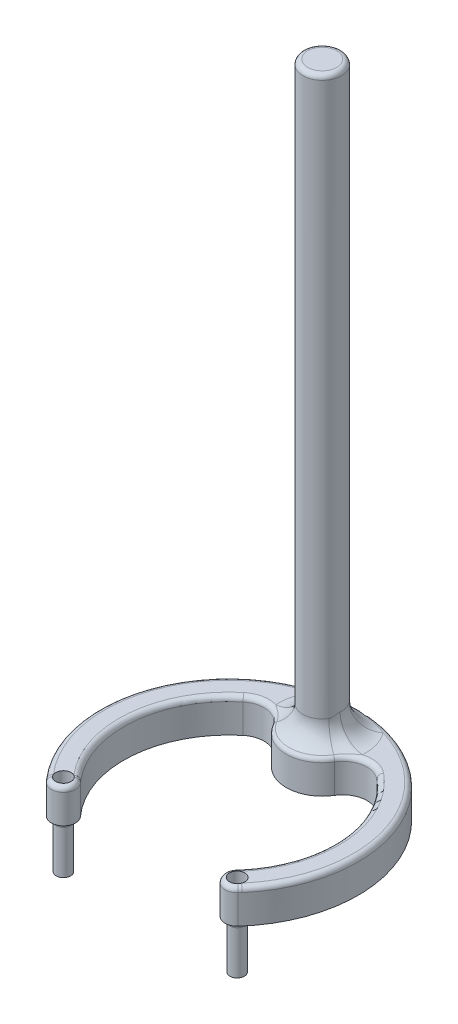
SolidWorks part; units mm, degrees
ref_plane "Front Plane" through (0, 0, 0) normal (0, 0, 1) x (1, 0, 0)
ref_plane "Top Plane" through (0, 0, 0) normal (0, 1, 0) x (1, 0, 0)
ref_plane "Right Plane" through (0, 0, 0) normal (1, 0, 0) x (0, 0, -1)
sketch "Sketch15" plane through (0, 0, 0) normal (0, 0, 1) x (1, 0, 0)
  point P0 (18, 0)
  point P1 (-18, 0)
  dimension "D1" = 18
  dimension "D2" = 18
sketch "Sketch17" plane through (0, 0, 0) normal (0, 1, 0) x (1, 0, 0)
  arc A0 (-19.8541, -1.6771) -> (-16.1459, 1.6771) centre (-18, 0) ccw
  arc A1 (16.1459, 1.6771) -> (19.8541, -1.6771) centre (18, 0) ccw
  arc A2 (19.8541, -1.6771) -> (-19.8541, -1.6771) centre (0, 16.2816) ccw
  arc A3 (16.1459, 1.6771) -> (13.851, 33.0785) centre (0, 16.2816) ccw
  arc A4 (16.1459, 1.6771) -> (19.8541, -1.6771) centre (18, 0) ccw
  arc A5 (-19.8541, -1.6771) -> (-16.1459, 1.6771) centre (-18, 0) ccw
  arc A6 (-6.3809, 31.7908) -> (6.3809, 31.7908) centre (0, 35.6141) ccw
  arc A7 (-13.851, 33.0785) -> (-16.1459, 1.6771) centre (0, 16.2816) ccw
  arc A8 (-6.3809, 31.7908) -> (-13.851, 33.0785) centre (-10.6699, 29.2209) ccw
  arc A9 (6.3809, 31.7908) -> (13.851, 33.0785) centre (10.6699, 29.2209) cw
  point P14 (-7.3474, 36.7755)
  dimension "D1" = 5
  dimension "D2" = 5
extrude "Boss-Extrude1" add sketch "Sketch17" along normal blind 7 contours A6 A9 A3 A1 A2 A0 A7 A8 region at (0, 0, -42.3498)
sketch "Sketch18" plane through (0, 7, 0) normal (0, 1, 0) x (1, 0, 0)
  circle A0 centre (0, 35.6141) radius 4
extrude "Boss-Extrude2" add sketch "Sketch18" along normal blind 120
sketch "Sketch19" plane through (0, 0, 0) normal (0, -1, 0) x (1, 0, 0)
  circle A0 centre (-18, 0) radius 1.5
  circle A1 centre (18, 0) radius 1.5
extrude "Boss-Extrude3" add sketch "Sketch19" along normal blind 10
sketch "Sketch20" plane through (0, 7, 0) normal (0, 1, 0) x (1, 0, 0)
  circle A0 centre (-18, 0) radius 0.95
  circle A1 centre (18, 0) radius 0.95
extrude "Cut-Extrude1" cut sketch "Sketch20" against normal through all
sketch "Sketch21" plane through (0, 7, 0) normal (0, 1, 0) x (1, 0, 0)
  circle A0 centre (-18, 0) radius 1.6
  circle A1 centre (18, 0) radius 1.6
extrude "Cut-Extrude2" cut sketch "Sketch21" against normal blind 3
fillet "Fillet1" radius 1 9 edges at (21.7133, 7, -17.8685) (9.8205, 7, -34.1482) (0, 7, -28.1754) (-9.8205, 7, -34.1482) (-21.7133, 7, -17.8685) (0, 127, -31.6141) (-18, 0, 1.5) (18, 0, 1.5) (0, 7, -43.0528)
fillet "Fillet2" radius 5 1 edges at (0, 7, -31.6141)
